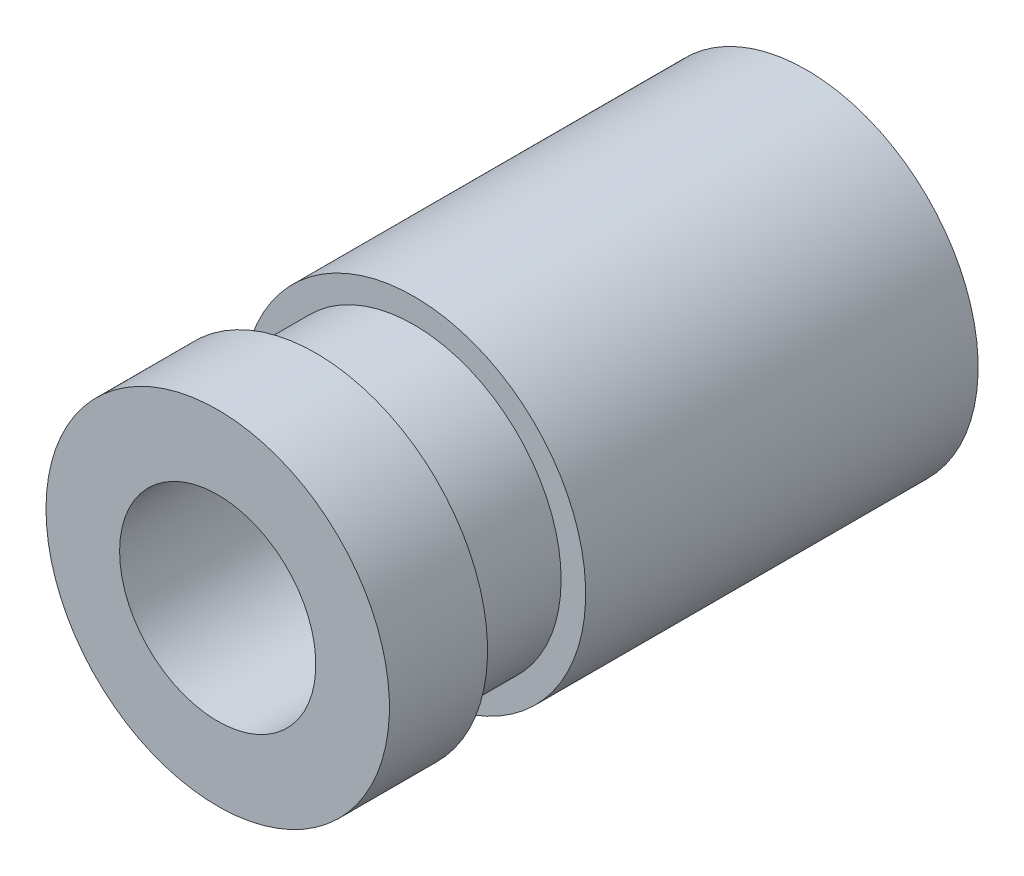
SolidWorks part; units mm, degrees
ref_plane "Front Plane" through (0, 0, 0) normal (0, 0, 1) x (1, 0, 0)
ref_plane "Top Plane" through (0, 0, 0) normal (0, 1, 0) x (1, 0, 0)
ref_plane "Right Plane" through (0, 0, 0) normal (1, 0, 0) x (0, 0, -1)
sketch "Sketch1" plane through (0, 0, 0) normal (0, 0, 1) x (1, 0, 0)
  circle A0 centre (0, 0) radius 2.2225
  circle A1 centre (0, 0) radius 1.27
  dimension "D1" = 2.54
  dimension "D2" = 4.445
extrude "Boss-Extrude1" add sketch "Sketch1" along normal blind 7.62
ref_plane "Plane1" through (0, 0, 6.35) normal (0, 0, 1) x (1, 0, 0)
sketch "Sketch2" plane through (0, 0, 6.35) normal (0, 0, 1) x (1, 0, 0)
  circle A0 centre (0, 0) radius 1.905
  circle A1 centre (0, 0) radius 2.2225
  dimension "D1" = 3.81
  dimension "D2" = 4.445
extrude "Cut-Extrude1" cut sketch "Sketch2" against normal blind 1.27
